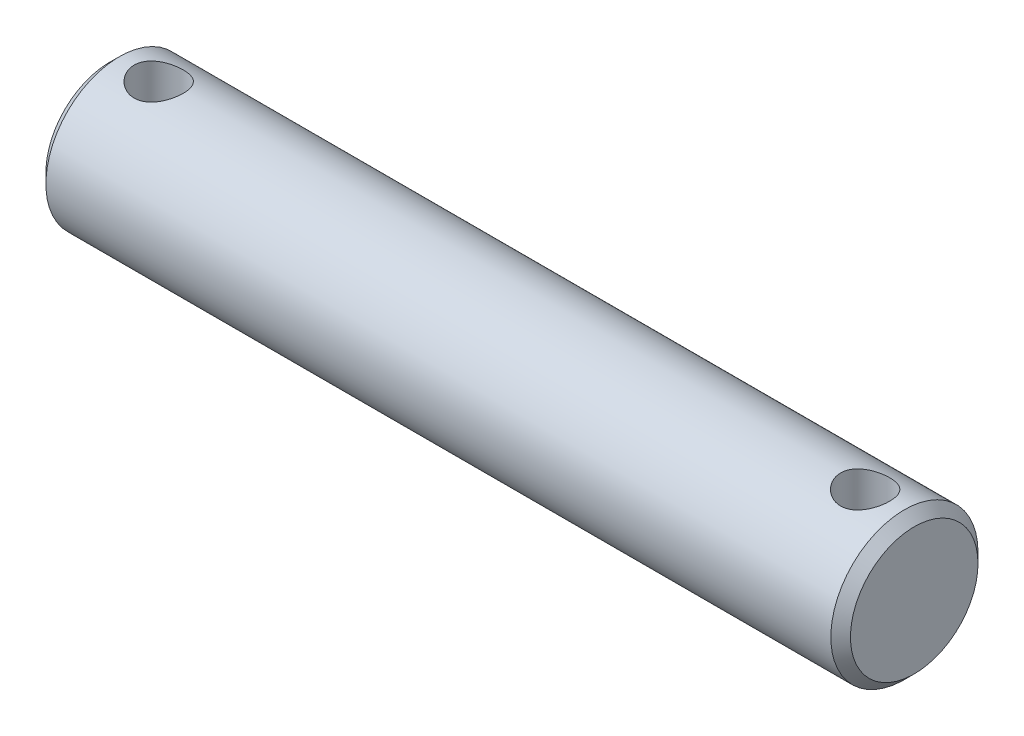
SolidWorks part; units mm, degrees
material "1.0050 (E295)"
ref_plane "Płaszczyzna przednia" through (0, 0, 0) normal (0, 0, 1) x (1, 0, 0)
ref_plane "Płaszczyzna górna" through (0, 0, 0) normal (0, 1, 0) x (1, 0, 0)
ref_plane "Płaszczyzna prawa" through (0, 0, 0) normal (1, 0, 0) x (0, 0, -1)
sketch "Szkic2" plane through (0, 0, 0) normal (1, 0, 0) x (0, 0, -1)
  circle A0 centre (0, 0) radius 7.5
  dimension "D1" = 15
extrude "Dodanie-wyciągnięcie1" add sketch "Szkic2" along normal blind 41 and the other way blind 41
sketch "Szkic3" plane through (0, 0, 0) normal (0, 1, 0) x (1, 0, 0)
  line L0 (-41, 7.5) -> (-41, -7.5) construction
  line L1 (41, -7.5) -> (41, 7.5) construction
  circle A0 centre (-36, 0) radius 2.5
  circle A1 centre (36, 0) radius 2.5
  dimension "D1" = 5
  dimension "D3" = 5
  dimension "D2" = 5
  dimension "D4" = 5
extrude "Wytnij-wyciągnięcie1" cut sketch "Szkic3" against normal up to next and the other way up to next
chamfer "Sfazowanie1" distance 1 angle 45 2 edges at (-41, 0, -7.5) (41, 0, -7.5)
